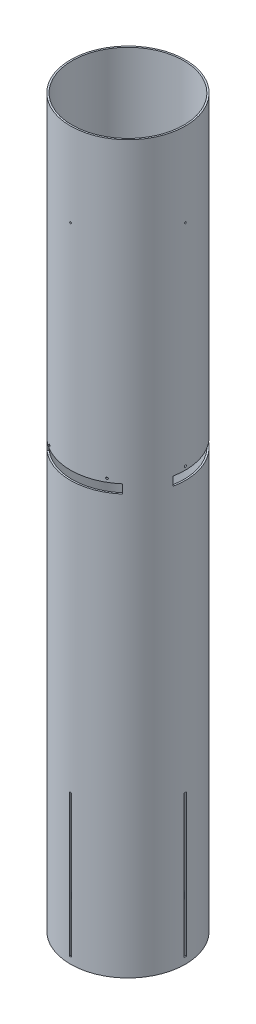
SolidWorks part; units mm, degrees
material "A-Glass Fiber"
ref_plane "Front Plane" through (0, 0, 0) normal (0, 0, 1) x (1, 0, 0)
ref_plane "Top Plane" through (0, 0, 0) normal (0, 1, 0) x (1, 0, 0)
ref_plane "Right Plane" through (0, 0, 0) normal (1, 0, 0) x (0, 0, -1)
sketch "Sketch1" plane through (0, 0, 0) normal (0, 1, 0) x (1, 0, 0)
  circle A0 centre (0, 0) radius 76.2
  circle A1 centre (0, 0) radius 78.359
  dimension "D1" = 152.4
  dimension "D2" = 156.718
extrude "Boss-Extrude1" add sketch "Sketch1" along normal blind 990.6
ref_plane "Plane1" through (0, 0, 0) normal (0.7071, 0, 0.7071) x (0.7071, 0, -0.7071)
ref_axis "Axis1" through (0, 990.6, 0) along (0, -1, 0)
sketch "Sketch2" plane through (0, 0, 0) normal (1, 0, 0) x (0, 0, -1)
  line L0 (0, 0) -> (0, 8.89)
  line L1 (1.5875, 8.89) -> (-1.5875, 8.89)
  line L2 (1.5875, 8.89) -> (1.5875, 203.2)
  line L3 (1.5875, 203.2) -> (-1.5875, 203.2)
  line L4 (-1.5875, 8.89) -> (-1.5875, 203.2)
  line L5 (1.5875, 8.89) -> (-1.5875, 203.2) construction
  line L6 (1.5875, 203.2) -> (-1.5875, 8.89) construction
  line L7 (78.359, 990.6) -> (-78.359, 990.6) construction
  line L8 (78.359, 990.6) -> (-78.359, 990.6)
  line L9 (0, 990.6) -> (0, 588.645)
  line L10 (-78.359, 0) -> (78.359, 0) construction
  circle A0 centre (0, 588.645) radius 1.3525
  circle A1 centre (0, 876.3) radius 1.0922
  point P0 (0, 106.045)
  dimension "D4" = 2.7051
  dimension "D6" = 2.1844
  dimension "D1" = 3.175
  dimension "D2" = 194.31
  dimension "D5" = 588.645
  dimension "D3" = 203.2
  dimension "D7" = 114.3
extrude "Fin Slots" cut sketch "Sketch2" against normal through all contours L4 L1 L2 L3 region at (0, 106.045, 0)
pattern_circular "CirPattern1" count 4 over 360 about axis through (0, 0, 0) along (0, 1, 0) of "Fin Slots" reverse direction yes
extrude "Cut-Extrude2" cut sketch "Sketch2<3>" against normal through all contours A0 region at (0, 589.5743, -0.9293)
sketch "Sketch2<3>" plane through (0, 0, 0) normal (1, 0, 0) x (0, 0, -1) same geometry as "Sketch2"
pattern_circular "CirPattern2" count 6 over 360 about axis through (0, 990.6, 0) along (0, -1, 0) of "Cut-Extrude2"
sketch "Sketch3" plane through (0, 0, 0) normal (0.7071, 0, 0.7071) x (0.7071, 0, -0.7071)
  line L0 (0, 0) -> (0, 127) construction
  circle A0 centre (0, 127) radius 3.175
  dimension "D1" = 6.35
  dimension "D2" = 127
extrude "Cut-Extrude3" cut sketch "Sketch3" against normal through all
ref_plane "Plane3" through (0, 583.8825, 0) normal (0, 1, 0) x (1, 0, 0)
sketch "Sketch7" plane through (0, 583.8825, 0) normal (0, 1, 0) x (1, 0, 0)
  line L0 (0, 0) -> (-76.8534, -15.2871)
  line L1 (0, 0) -> (0, 93.232) construction
  line L2 (0, 0) -> (-25.1877, 74.2005)
  line L3 (-78.359, 0) -> (0, 0) construction
  arc A0 (-78.3473, 1.3526) -> (-78.3473, -1.3525) centre (0, 0) ccw construction
  circle A1 centre (0, 0) radius 76.2 construction
  circle A2 centre (0, 0) radius 78.359
  circle A3 centre (0, 0) radius 78.359
  circle A4 centre (0, 0) radius 76.2
  circle A5 centre (0, 0) radius 78.359 construction
  arc A6 (-38.0023, 68.527) -> (-40.345, 67.1745) centre (0, 0) ccw construction
  arc A7 (-78.3473, 1.3526) -> (-78.3473, -1.3525) centre (0, 0) ccw
  arc A8 (-38.0023, 68.527) -> (-40.345, 67.1745) centre (0, 0) ccw
  dimension "D1" = 82.5
  dimension "D3" = 11.25
  dimension "D2" = 0
extrude "Cut-Extrude4" cut sketch "Sketch7" against normal blind 12.065 contours A4 A3 L0 region at (-75.9984, 583.8825, 14.0521)
pattern_circular "CirPattern3" count 3 over 360 about axis through (0, 990.6, 0) along (0, -1, 0) of "Cut-Extrude4"
extrude "Shear Screw Holes" cut sketch "Sketch2<4>" against normal through all contours L9 A1 | L9 A1 region at (0, 876.3, -0.4635) region at (0, 876.3, 0.4635)
sketch "Sketch2<4>" plane through (0, 0, 0) normal (1, 0, 0) x (0, 0, -1) same geometry as "Sketch2"
pattern_circular "Shear Screw Pattern" count 4 over 360 about axis through (0, 990.6, 0) along (0, -1, 0) of "Shear Screw Holes"
equation "\"D1@Boss-Extrude1\" = \"Aft_Section_Length\""
equation "\"AB_Coupler_OD_Length\"= 1in"
equation "\"AB_Coupling_Section_Length\"= 0.375in"
equation "\"AB_Coupler_Length\"= \"AB_Coupler_OD_Length\" + \"AB_Coupling_Section_Length\" * 2"
equation "\"AB_Coupler_Num_Screws\"= 6"
equation "\"AB_Coupling_Screw_Diameter\"= 0.1065in"
equation "\"Aft_Section_Length\"= 39in"
equation "\"D4@Sketch2\"=\"AB_Coupling_Screw_Diameter\""
equation "\"D1@CirPattern2\"=\"AB_Coupler_Num_Screws\""
equation "\"Rail_Nut_From_Bottom\"= 5in"
equation "\"Rail_Nut_Diam\"= 0.25in"
equation "\"D1@Sketch3\"=\"Rail_Nut_Diam\""
equation "\"D2@Sketch3\"=\"Rail_Nut_From_Bottom\""
equation "\"AB_BKHD_Thickness\" = 0.375in"
equation "\"AB_Mount_From_Bottom\" = 23.175in"
equation "\"Cutout_Angle\"=80"
equation "\"Shear_Screw_Diameter\" = 0.086in"
equation "\"D6@Sketch2\"=\"Shear_Screw_Diameter\""
equation "\"Shear_Screw_Coupler_Location\" = 4.5in"
equation "\"D7@Sketch2\"=\"Shear_Screw_Coupler_Location\""
